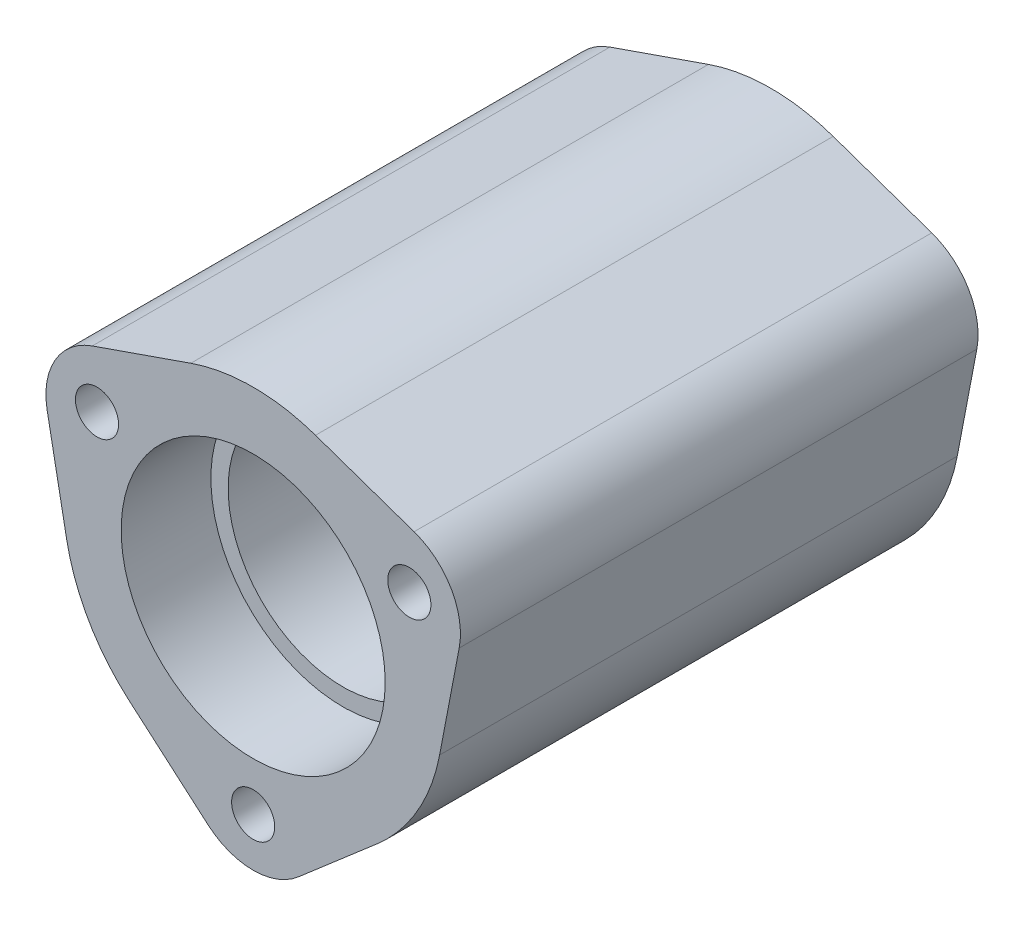
SolidWorks part; units mm, degrees
ref_plane "Спереди" through (0, 0, 0) normal (0, 0, 1) x (1, 0, 0)
ref_plane "Сверху" through (0, 0, 0) normal (0, 1, 0) x (1, 0, 0)
ref_plane "Справа" through (0, 0, 0) normal (1, 0, 0) x (0, 0, -1)
sketch "Эскиз1" plane through (0, 0, 0) normal (0, 0, 1) x (1, 0, 0)
  line L0 (-9.3248, 8.403) -> (-3.6137, 10.3895)
  line L1 (0, 0) -> (0, -9.25) construction
  line L2 (-11.9396, 3.874) -> (-10.8044, -2.0651)
  line L3 (2.6148, -12.277) -> (7.1907, -8.3243)
  line L4 (-2.6148, -12.277) -> (-7.1907, -8.3243)
  line L5 (11.9396, 3.874) -> (10.8044, -2.0651)
  line L6 (9.3248, 8.403) -> (3.6137, 10.3895)
  circle A0 centre (0, 0) radius 11 construction
  arc A1 (7.1907, -8.3243) -> (10.8044, -2.0651) centre (0, 0) ccw
  arc A2 (-9.3248, 8.403) -> (-11.9396, 3.874) centre (-8.0107, 4.625) ccw
  arc A3 (-2.6148, -12.277) -> (2.6148, -12.277) centre (0, -9.25) ccw
  arc A4 (11.9396, 3.874) -> (9.3248, 8.403) centre (8.0107, 4.625) ccw
  arc A5 (3.6137, 10.3895) -> (-3.6137, 10.3895) centre (0, 0) ccw
  arc A6 (-10.8044, -2.0651) -> (-7.1907, -8.3243) centre (0, 0) ccw
  circle A7 centre (0, 0) radius 9.25 construction
  point P24 (0, 0)
  dimension "D1" = 4
  dimension "D2" = 22
  dimension "D3" = 3
  dimension "D4" = 18.5
extrude "тело" add sketch "Эскиз1" along normal blind 15 and the other way blind 15
sketch "Эскиз2" plane through (0, 0, 15) normal (0, 0, 1) x (1, 0, 0)
  circle A0 centre (0, 0) radius 7.65
  dimension "D1" = 15.3
extrude "углубление под подшипник" cut sketch "Эскиз2" against normal blind 5.2
mirror "Углубление под подшипник с обратной стороны" about plane through (0, 0, 0) normal (0, 0, 1) of "углубление под подшипник"
sketch "Эскиз3" plane through (0, 0, 9.8) normal (0, 0, 1) x (1, 0, 0)
  circle A0 centre (0, 0) radius 6.65
  circle A1 centre (0, 0) radius 7.65 construction
  dimension "D1" = 1
extrude "сквозное отверстие" cut sketch "Эскиз3" against normal through all
sketch "Эскиз4" plane through (0, 0, 15) normal (0, 0, 1) x (1, 0, 0)
  line L0 (0, -13.25) -> (0, -7.65) construction
  circle A0 centre (-9.05, 5.225) radius 1.25
  circle A1 centre (0, -10.45) radius 1.25
  circle A2 centre (9.05, 5.225) radius 1.25
  arc A3 (-2.6148, -12.277) -> (2.6148, -12.277) centre (0, -9.25) ccw construction
  circle A4 centre (0, 0) radius 7.65 construction
  circle A5 centre (0, 0) radius 7.65 construction
  point P8 (0, 0)
  point P18 (0, -10.45)
  dimension "D1" = 2.5
  dimension "D2" = 3
extrude "отверстия для шурупов" cut sketch "Эскиз4" against normal through all
